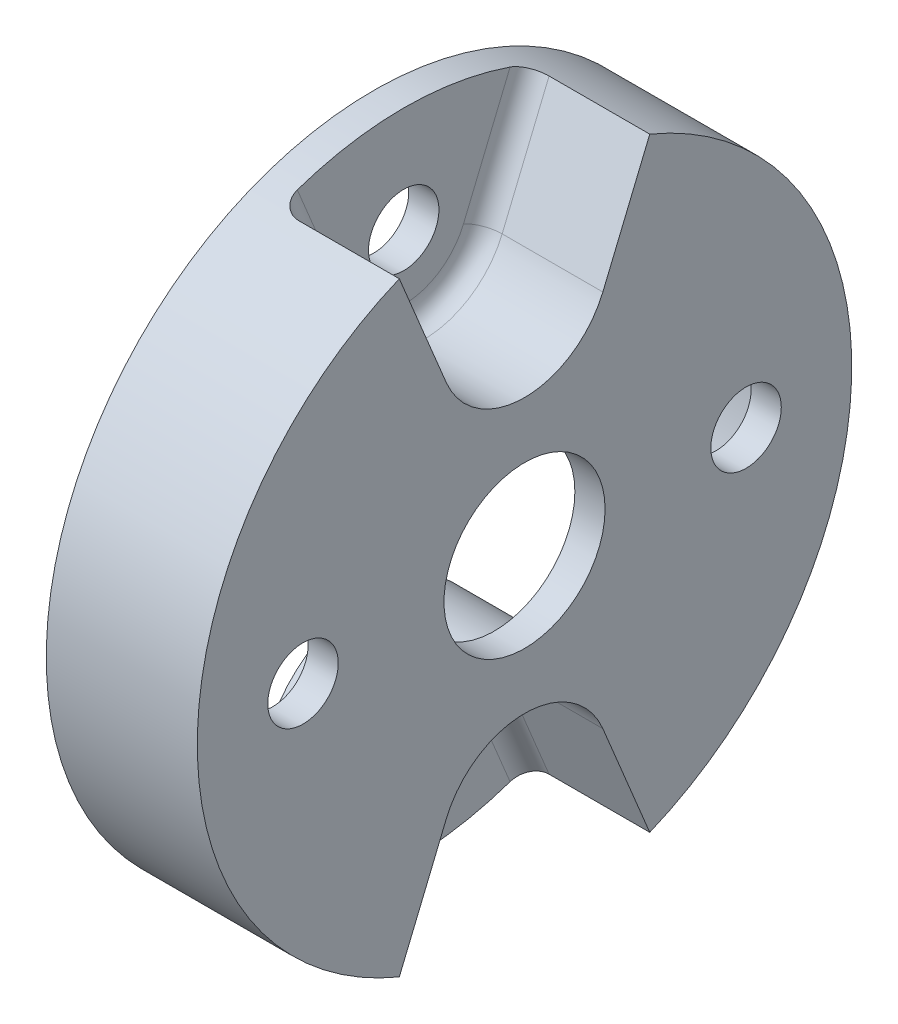
SolidWorks part; units mm, degrees
ref_plane "Front Plane" through (0, 0, 0) normal (0, 0, 1) x (1, 0, 0)
ref_plane "Top Plane" through (0, 0, 0) normal (0, 1, 0) x (1, 0, 0)
ref_plane "Right Plane" through (0, 0, 0) normal (1, 0, 0) x (0, 0, -1)
sketch "Sketch1" plane through (0, 0, 0) normal (1, 0, 0) x (0, 0, -1)
  circle A0 centre (0, 0) radius 32.5
  dimension "D1" = 65
extrude "Boss-Extrude1" add sketch "Sketch1" along normal blind 15
sketch "Sketch2" plane through (15, 0, 0) normal (1, 0, 0) x (0, 0, -1)
  line L0 (-12.4372, 30.0261) -> (-7.7782, 18.7782)
  line L1 (7.7782, 18.7782) -> (12.4372, 30.0261)
  line L2 (0, 0) -> (0, 22) construction
  line L3 (0, 0) -> (37.7248, 0) construction
  line L4 (-12.4372, -30.0261) -> (-7.7782, -18.7782)
  line L5 (7.7782, -18.7782) -> (12.4372, -30.0261)
  line L6 (-14.0023, 25.9651) -> (-10.5498, 17.6301)
  line L7 (10.5498, 17.6301) -> (14.0023, 25.9651)
  line L8 (-14.0023, -25.9651) -> (-10.5498, -17.6301)
  line L9 (10.5498, -17.6301) -> (14.0023, -25.9651)
  line L10 (-15.2089, 28.878) -> (-10.5498, 17.6301) construction
  line L11 (10.5498, 17.6301) -> (15.2089, 28.878) construction
  line L12 (10.5498, -17.6301) -> (15.2089, -28.878) construction
  line L13 (-15.2089, -28.878) -> (-10.5498, -17.6301) construction
  line L14 (-7.7782, 18.7782) -> (0, 0) construction
  line L15 (0, 0) -> (7.7782, 18.7782) construction
  circle A0 centre (0, 0) radius 32.5 construction
  arc A1 (-7.7782, 18.7782) -> (7.7782, 18.7782) centre (0, 22) ccw
  circle A2 centre (0, 0) radius 22 construction
  circle A3 centre (0, 22) radius 3.5
  circle A4 centre (0, 0) radius 8
  arc A5 (-7.7782, -18.7782) -> (7.7782, -18.7782) centre (0, -22) cw
  circle A7 centre (22, 0) radius 3.5
  circle A8 centre (0, -22) radius 3.5
  circle A9 centre (-22, 0) radius 3.5
  arc A10 (-10.5498, 17.6301) -> (10.5498, 17.6301) centre (0, 22) ccw
  arc A11 (-10.5498, -17.6301) -> (10.5498, -17.6301) centre (0, -22) cw
  circle A12 centre (0, 0) radius 29.5
  point P28 (0, 0)
  circle M13 centre (0, 0) radius 32.5
  dimension "D2" = 44
  dimension "D3" = 7
  dimension "D4" = 16
  dimension "D8" = 3
  dimension "D9" = 45
  dimension "D1" = 45
  dimension "D6" = 3
  dimension "D7" = 3
  dimension "D5" = 4
extrude "Cut-Extrude1" cut sketch "Sketch2" against normal offset from surface (12 mm away) 3 contours A12 L1 L0 M13 | L1 A12 L0 A1 A3 | L4 A12 L5 A5 A8 | A12 L4 L5 M13 region at (15, 30.2329, 0) region at (15, 29.2237, 0) region at (15, -30.2329, 0) region at (15, -23.122, 9.2784) up to face at (0, 0, -32.5)
extrude "Cut-Extrude2" cut sketch "Sketch2<3>" against normal through all contours A3 | A8 | A9 | A7 | A4 region at (15, 22, 0) region at (15, 0, 0) region at (15, 0, -22) region at (15, -22, 0) region at (15, 0, 22)
sketch "Sketch2<3>" plane through (15, 0, 0) normal (1, 0, 0) x (0, 0, -1) same geometry as "Sketch2"
extrude "Cut-Extrude3" cut sketch "Sketch2<4>" along normal offset from surface (12 mm away) 3 from surface contours L6 A12 L8 A11 L9 L7 A10 A9 A7 A4 region at (15, 21.4968, 13.0022) up to face at (15, 0, -8) starting at face at (0, 22, -3.5)
sketch "Sketch2<4>" plane through (15, 0, 0) normal (1, 0, 0) x (0, 0, -1) same geometry as "Sketch2"
fillet "Fillet1" radius 2 12 edges at (12, -21.7976, -12.276) (12, -10.581, 0) (12, 21.7976, 12.276) (12, 10.581, 0) (12, -21.7976, 12.276) (6, -25.9651, 14.0023) (6, -25.9651, -14.0023) (12, 0, -29.5) (12, 0, 29.5) (6, 25.9651, -14.0023) (6, 25.9651, 14.0023) (12, 21.7976, -12.276)
fillet "Fillet2" radius 2 6 edges at (3, -24.4021, 10.1077) (3, -13.581, 0) (3, 24.4021, 10.1077) (3, 13.581, 0) (3, -24.4021, -10.1077) (3, 24.4021, -10.1077)
